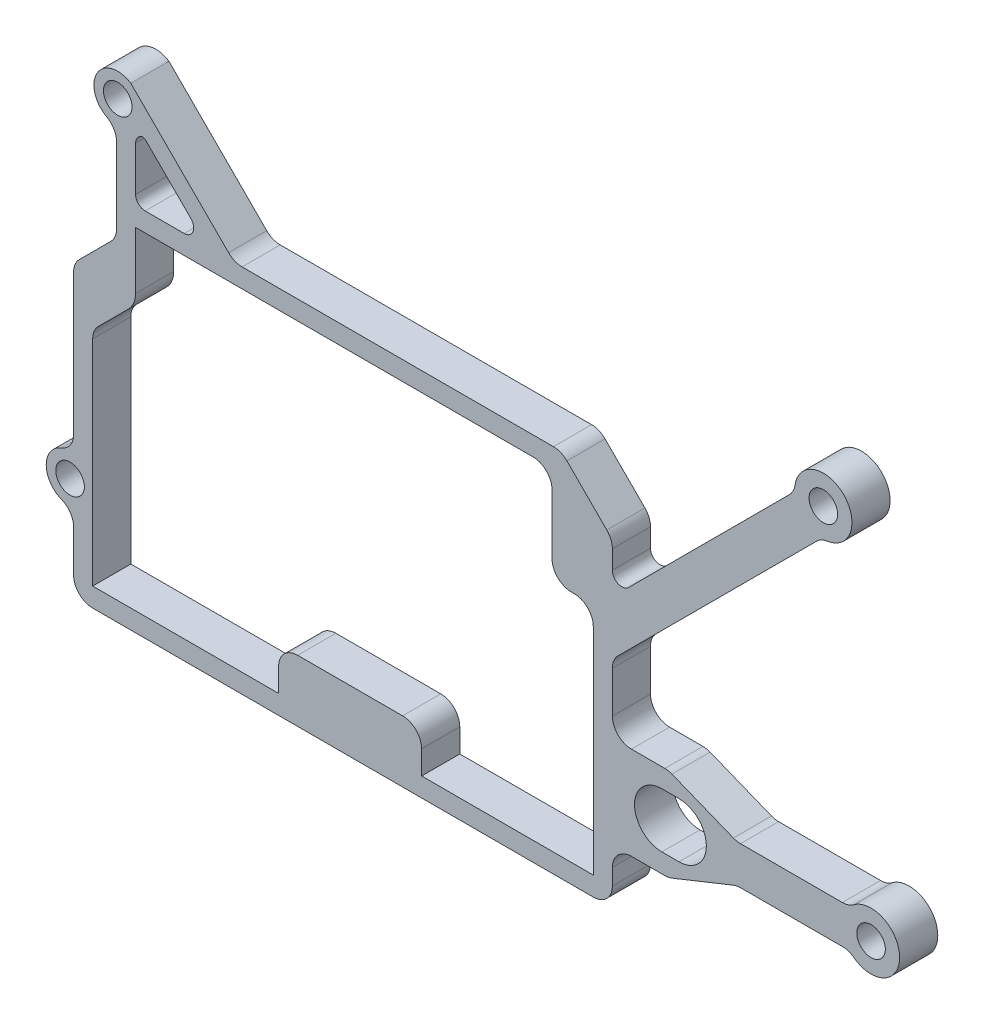
SolidWorks part; units mm, degrees
ref_plane "Front Plane" through (0, 0, 0) normal (1, 0, 0) x (0, 1, 0)
ref_plane "Top Plane" through (0, 0, 0) normal (0, 0, 1) x (0, 1, 0)
ref_plane "Right Plane" through (0, 0, 0) normal (0, 1, 0) x (-1, 0, 0)
ref_axis "x axis" through (-88.99, 0, 0) along (1, 0, 0)
ref_axis "y xxis" through (0, 88.99, 0) along (0, -1, 0)
ref_axis "z axis" through (0, 0, 55) along (0, 0, -1)
sketch "Sketch2" plane through (0, 0, 0) normal (0, 0, 1) x (0, 1, 0)
  line L0 (-37, 37) -> (37, 37) construction
  line L1 (37, 37) -> (37, -37) construction
  line L2 (37, -37) -> (-37, -37) construction
  line L3 (-37, -37) -> (-37, 37) construction
  line L4 (0, 42) -> (0, 37) construction
  line L5 (-42, 0) -> (-37, 0) construction
  line L6 (42, 0) -> (37, 0) construction
  line L7 (0, -42) -> (0, -37) construction
  line L8 (-37, 37) -> (37, -37) construction
  point P0 (37, 37)
  point P1 (0, 42)
  point P2 (42, 0)
  point P3 (0, -42)
  point P4 (-37, -37)
  point P5 (37, -37)
  point P6 (-42, 0)
  point P7 (-37, 37)
  point P20 (0, 0)
  point P21 (-45.7825, 0)
  point P23 (0, 0)
  dimension "D1" = 74
  dimension "D2" = 42
sketch "Sketch3" plane through (0, 0, 0) normal (0, 0, 1) x (0, 1, 0)
  line L0 (20.2489, -11.3728) -> (20.2489, 37.6272) construction
  line L1 (20.2489, 13.1272) -> (-3.5511, 13.1272) construction
  line L2 (-3.5511, 13.1272) -> (-7.2511, 13.1272) construction
  line L3 (-7.2511, 17.1272) -> (-7.2511, 9.1272) construction
  point P1 (20.2489, -11.3728)
  point P2 (20.2489, 37.6272)
  point P9 (-7.2511, 13.1272)
  point P10 (9.3275, 48.8354)
  point P11 (23.3219, -14.0307)
  point P12 (0, 0)
  point P13 (20.2334, 35.5403)
  point P14 (20.2489, 37.6272)
  point P15 (0, 0)
  dimension "D1" = 23.8
  dimension "D2" = 24.5
  dimension "D3" = 3.7
  dimension "D4" = 4
sketch "Sketch4" plane through (0, 0, 0) normal (0, 0, 1) x (0, 1, 0)
  line L0 (-8.571, -12.8728) -> (-8.571, 5.1272)
  line L2 (-2, -39.7639) -> (-2, -27.9206)
  line L3 (-2, -27.9206) -> (-4.8678, -20.7641)
  line L4 (26.2489, -4.7025) -> (26.2489, 35.1272)
  line L5 (15.9928, -12.8728) -> (-8.571, -12.8728)
  line L6 (-8.571, 20.1272) -> (-4.1074, 20.1272)
  line L7 (-4.1074, 20.1272) -> (-4.1074, 5.1272)
  line L8 (-4.1074, 5.1272) -> (-8.571, 5.1272)
  line L9 (-8.571, 20.1272) -> (-8.571, 39.6272)
  line L10 (-8.571, 39.6272) -> (14.7133, 39.6272)
  line L11 (14.7133, 39.6272) -> (18.4811, 35.8594)
  line L12 (20.2489, 35.1272) -> (26.2489, 35.1272)
  line L13 (-10.571, -14.8728) -> (-4.8678, -14.8728)
  line L14 (-10.571, -14.8728) -> (-10.571, 41.6272)
  line L15 (4.8678, -14.8728) -> (12.0444, -14.8728)
  line L16 (26.2489, 10.1641) -> (28.2489, 10.1641) construction
  line L17 (28.2489, -9.5183) -> (28.2489, 24.7891)
  line L18 (28.2489, 24.7891) -> (39.0939, 35.6341)
  line L19 (-10.571, 41.6272) -> (-2.472, 41.6272)
  line L20 (34.5032, 37.1272) -> (24.2844, 37.1272)
  line L21 (34.0046, -36.8331) -> (12.0444, -14.8728)
  line L22 (36.8331, -34.0046) -> (17.7012, -14.8728)
  line L23 (6.7613, -14.8728) -> (6.7613, -12.8728) construction
  line L24 (19.7844, 41.6272) -> (24.2844, 37.1272)
  line L25 (-4.8678, -20.7641) -> (-4.8678, -14.8728)
  line L26 (0, -42) -> (0, -18.1353) construction
  line L27 (4.8678, -20.7641) -> (4.8678, -14.8728)
  line L28 (2, -27.9206) -> (4.8678, -20.7641)
  line L29 (2, -27.9206) -> (2, -39.7639)
  line L30 (0, -20.0652) -> (0, -21.8608) construction
  line L31 (2.8678, -20.0652) -> (2.8678, -21.8608)
  line L32 (-2.8678, -20.0652) -> (-2.8678, -21.8608)
  line L33 (-7.2511, -14.8728) -> (-7.2511, -12.8728) construction
  line L34 (-10.571, -9.8564) -> (-8.571, -9.8564) construction
  line L35 (2.8678, 39.6272) -> (2.8678, 41.6272) construction
  line L36 (-10.571, 30.2348) -> (-8.571, 30.2348) construction
  line L37 (-4.8678, -20.3391) -> (-2.8678, -20.3391) construction
  line L38 (17.7012, -14.8728) -> (22.8943, -14.8728)
  line L39 (15.9928, -12.8728) -> (15.9928, -8.5508)
  line L40 (15.9928, -8.5508) -> (26.2489, -8.5508)
  line L41 (26.2489, -8.5508) -> (26.2489, -4.7025)
  line L42 (28.2489, 27.6175) -> (28.2489, 35.1272)
  line L43 (2.472, 41.6272) -> (19.7844, 41.6272)
  line L44 (28.2489, 35.1272) -> (34.9053, 35.1272)
  line L45 (34.9053, 35.1272) -> (34.9053, 34.274)
  line L46 (34.9053, 34.274) -> (28.2489, 27.6175)
  line L47 (34.0392, 30.5794) -> (32.6249, 31.9936) construction
  line L48 (30.9894, 35.1272) -> (30.9894, 37.1272) construction
  line L49 (20.2489, 37.6272) -> (22.0166, 39.395) construction
  line L50 (20.2489, 37.6272) -> (18.4811, 35.8594) construction
  line L51 (18.9623, 44.1507) -> (18.9623, 44.1603) construction
  line L52 (22.8943, -14.8728) -> (28.2489, -9.5183)
  line L53 (27.7556, -30.5841) -> (30.5841, -27.7556) construction
  line L54 (-2, -33.8423) -> (2, -33.8423) construction
  line L55 (29.1698, -29.1698) -> (37, -37) construction
  arc A0 (38.3659, 34.9061) -> (34.5032, 37.1272) centre (37, 37) ccw
  arc A1 (18.4811, 35.8594) -> (20.2489, 35.1272) centre (20.2489, 37.6272) ccw
  arc A3 (-2, -39.7639) -> (2, -39.7639) centre (0, -42) ccw
  arc A8 (34.0046, -36.8331) -> (36.8331, -34.0046) centre (37, -37) ccw
  arc A12 (2.8678, -20.0652) -> (-2.8678, -20.0652) centre (0, -20.0652) ccw
  arc A13 (-2.8678, -21.8608) -> (2.8678, -21.8608) centre (0, -21.8608) ccw
  arc A14 (2.472, 41.6272) -> (-2.472, 41.6272) centre (0, 42) ccw
  point P56 (0, -20.963)
  dimension "D2" = 5
  dimension "D3" = 5
  dimension "D5" = 6
  dimension "D7" = 15
  dimension "D17" = 135
  dimension "D18" = 4
  dimension "D10" = 2
  dimension "D11" = 135
  dimension "D12" = 4
  dimension "D15" = 135
  dimension "D16" = 45
  dimension "D19" = 90
extrude "Boss-Extrude1" add sketch "Sketch4" along normal blind 4 contours A8 L17 L18 A0 L14 A3 L15 L11 A1 L12 L4 L5 L0 L8 L7 L6 L9 L10 region at (33.8423, -0.972, 0)
sketch "Sketch5" plane through (0, 0, 4) normal (0, 0, 1) x (1, 0, 0)
  circle A0 centre (-37, 37) radius 1.5
  circle A1 centre (-42, 0) radius 1.5
  circle A2 centre (37, 37) radius 1.5
  circle A3 centre (42, 0) radius 1.5
  dimension "D1" = 3
extrude "Cut-Extrude1" cut sketch "Sketch5" against normal blind 3
sketch "Sketch6" plane through (0, 0, 0) normal (0, 0, -1) x (1, 0, 0)
  circle A0 centre (-17.1272, 7.2511) radius 1.5
  circle A1 centre (-9.1272, 7.2511) radius 1.5
  circle A2 centre (11.3728, -20.2489) radius 1.5
  circle A3 centre (-37.6272, -20.2489) radius 1.5
  dimension "D1" = 3
extrude "Cut-Extrude2" cut sketch "Sketch6" against normal blind 3
fillet "Fillet1" radius 2 27 edges at (-5.1272, -4.1074, 2) (-20.1272, -4.1074, 2) (-39.6272, 14.7133, 2) (-41.6272, 19.7844, 2) (-24.7891, 28.2489, 2) (8.5508, 26.2489, 2) (8.5508, 15.9928, 2) (12.8728, 15.9928, 2) (14.8728, 12.0444, 2) (14.8728, 4.8678, 2) (20.7641, 4.8678, 2) (27.9206, 2, 2) (27.9206, -2, 2) (20.7641, -4.8678, 2) (14.8728, -4.8678, 2) (14.8728, -10.571, 2) (-41.6272, -10.571, 2) (-41.6272, 2.472, 2) (-41.6272, -2.472, 2) (-37.1272, 34.5032, 2) (-37.1272, 24.2844, 2) (34.0046, 36.8331, 2) (36.8331, 34.0046, 2) (39.7639, 2, 2) (39.7639, -2, 2) (14.8728, 22.8943, 2) (9.5183, 28.2489, 2)
fillet "Fillet2" radius 1 5 edges at (14.8728, 17.7012, 2) (-34.274, 34.9053, 2) (-35.1272, 34.9053, 2) (-35.1272, 28.2489, 2) (-27.6175, 28.2489, 2)
